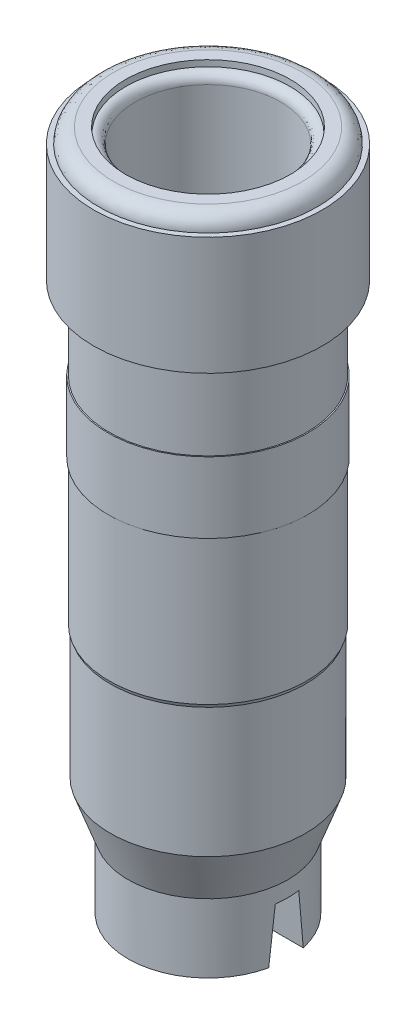
SolidWorks part; units mm, degrees
ref_plane "Front" through (0, 0, 0) normal (0, 0, 1) x (1, 0, 0)
ref_plane "Top" through (0, 0, 0) normal (0, 1, 0) x (1, 0, 0)
ref_plane "Right" through (0, 0, 0) normal (1, 0, 0) x (0, 0, -1)
sketch "Esboço1" plane through (0, 0, 0) normal (0, 0, 1) x (1, 0, 0)
  line L0 (0, 0) -> (0, 23.1) construction
  line L6 (-3.37, 10.5013) -> (-3.41, 10.5013)
  line L7 (-3.9, 18.6) -> (-3.37, 18.6)
  line L8 (-3.37, 18.6) -> (-3.37, 15.8)
  line L9 (-3.37, 4.1013) -> (-2.725, 2.3292)
  line L10 (-2.725, 2.3292) -> (-2.725, 0)
  line L15 (-3.37, 15.8) -> (-3.43, 15.8)
  line L16 (-3.37, 13.4) -> (-3.43, 13.4)
  line L17 (-3.41, 10.5013) -> (-3.41, 8.1013)
  line L18 (-3.41, 8.1013) -> (-3.37, 8.1013)
  line L19 (-3.37, 13.4) -> (-3.37, 10.5013)
  line L20 (-3.37, 8.1013) -> (-3.37, 4.1013)
  line L21 (-3.43, 13.4) -> (-3.43, 15.8)
  line L22 (-3.9, 22.6) -> (-3.9, 18.6)
  line L23 (-2.725, 0) -> (0, 0)
  line L24 (-3.9, 22.6) -> (-3.725, 22.6)
  line L25 (0, 23.1) -> (0, 0) construction
  line L27 (-3.225, 23.1) -> (0, 23.1)
  line L29 (0, 23.1) -> (0, 0)
  arc A1 (-3.225, 23.1) -> (-3.725, 22.6) centre (-3.225, 22.6) ccw
  point P5 (-3.725, 23.1)
  point P20 (-3.37, 17.2)
  dimension "D9" = 0.5
  dimension "D8" = 1
  dimension "D3" = 22.6
  dimension "D4" = 4
  dimension "D5" = 5.45
  dimension "D6" = 20.2708
  dimension "D7" = 0.5
  dimension "D10" = 0.5
  dimension "D11" = 2.8
  dimension "D12" = 2.4
  dimension "D13" = 20
  dimension "D14" = 3.725
  dimension "D16" = 7.8
  dimension "D17" = 0.06
  dimension "D18" = 6.74
  dimension "D19" = 2.4
  dimension "D20" = 4
  dimension "D21" = 6.74
  dimension "D22" = 0.04
  dimension "D23" = 6.82
  dimension "D24" = 6.86
revolve "Revolução1" add sketch "Esboço1" angle 360 about L0
sketch "Esboço3" plane through (0, 0, 0) normal (0, -1, 0) x (1, 0, 0)
  circle A0 centre (0, 0) radius 1.5
  dimension "D1" = 3
extrude "Corte-extrusão1" cut sketch "Esboço3" against normal blind 1.8
sketch "Esboço5" plane through (0, 0, 0) normal (1, 0, 0) x (0, 0, -1)
  line L0 (0, 0) -> (0, 22.6) construction
  line L1 (-1.5, 0) -> (1.5, 0) construction
  line L2 (3.9, 22.6) -> (-3.9, 22.6) construction
  line L3 (-0.5892, 0) -> (0.5892, 0)
  line L4 (0.5892, 0) -> (0.4, 1.8)
  line L5 (0.4, 1.8) -> (-0.4, 1.8)
  line L6 (-0.5892, 0) -> (-0.4, 1.8)
  point P10 (0, 1.8)
  dimension "D1" = 0.8
  dimension "D2" = 1.8
  dimension "D3" = 6
extrude "Corte-extrusão2" cut sketch "Esboço5" against normal through all both and the other way through all
sketch "Esboço6" plane through (0, 0, 0) normal (0, 0, 1) x (1, 0, 0)
  line L0 (3.9, 22.6) -> (-3.9, 22.6) construction
  line L1 (2.8105, 23.1) -> (0, 23.1)
  line L2 (0, 22.6) -> (0, 0) construction
  line L3 (0, 23.1) -> (0, 22.6)
  line L4 (2.46, 10.9) -> (2.26, 10.9)
  line L5 (2.48, 22.6) -> (2.48, 17.9)
  line L6 (2.45, 9.1035) -> (1.75, 6.4911)
  line L7 (1.75, 6.4911) -> (1.75, 3.4)
  line L8 (1.75, 3.4) -> (1.5, 3.4)
  line L9 (2.8, 22.8993) -> (2.8105, 23.1)
  line L10 (0, 22.6) -> (0, 23.1) construction
  line L11 (3.225, 23.1) -> (-3.225, 23.1) construction
  line L12 (0, 22.6) -> (0, 3.9)
  line L14 (2.26, 10.9) -> (2.45, 9.8225)
  line L15 (2.465, 13.2) -> (2.265, 13.2)
  line L16 (2.265, 13.2) -> (2.46, 12.0941)
  line L17 (2.48, 17.9) -> (2.28, 17.9)
  line L18 (2.28, 17.9) -> (2.48, 16.7657)
  line L19 (2.45, 9.8225) -> (2.45, 9.1035)
  line L20 (2.46, 12.0941) -> (2.46, 10.9)
  line L21 (2.48, 16.7657) -> (2.465, 13.2)
  line L22 (-2.6605, 0) -> (2.6605, 0) construction
  line L23 (0, 0) -> (0, 3.4) construction
  arc A0 (2.48, 22.6) -> (2.8, 22.8993) centre (2.78, 22.6) cw
  arc A1 (1.5, 3.4) -> (0, 3.9) centre (0, 1.4) ccw
  dimension "D7" = 0.2
  dimension "D16" = 15
  dimension "D10" = 0.2
  dimension "D19" = 0.3
  dimension "D14" = 2.5
  dimension "D3" = 9.4
  dimension "D4" = 10
  dimension "D5" = 0.2
  dimension "D6" = 11.7
  dimension "D8" = 10
  dimension "D9" = 15
  dimension "D11" = 10
  dimension "D12" = 3.0911
  dimension "D13" = 0.5
  dimension "D15" = 19.7
  dimension "D17" = 3.5
  dimension "D18" = 3
  dimension "D20" = 5.6
  dimension "D21" = 3
  dimension "D22" = 4.7
  dimension "D23" = 2.48
  dimension "D24" = 2.46
  dimension "D25" = 2.46
  dimension "D26" = 4.93
  dimension "D27" = 4.9
  dimension "D28" = 4.9
revolve "Corte-Revolução1" cut sketch "Esboço6" angle 360 about L2
fillet "Filete1" radius 0.2 1 edges at (-1.75, 3.4, 0)
sketch "Esboço9" plane through (0, 0, 0) normal (0, 0, 1) x (1, 0, 0)
  line L0 (0, 0) -> (0, 43.223) construction
  line L5 (-6.0049, 22.6) -> (-3.9, 22.6)
  line L6 (-3.37, 8.4914) -> (-3.33, 8.3815)
  line L7 (-3.9, 18.6) -> (-3.37, 18.6)
  line L8 (-3.37, 18.6) -> (-3.37, 15.8)
  line L9 (-3.33, 3.9914) -> (-2.725, 2.3292)
  line L15 (-3.37, 15.8) -> (-3.41, 15.8)
  line L16 (-3.37, 13.4) -> (-3.41, 13.4)
  line L17 (-3.33, 8.3815) -> (-3.33, 3.9914)
  line L18 (-2.6605, 0) -> (2.6605, 0) construction
  line L19 (-2.725, 2.3292) -> (-2.725, 1.8) construction
  line L20 (-3.37, 13.4) -> (-3.37, 8.4914)
  line L21 (-3.41, 13.4) -> (-3.41, 15.8)
  line L22 (-3.37, 4.1013) -> (-2.725, 2.3292) construction
  line L23 (-3.9, 22.6) -> (-3.9, 18.6)
  line L26 (-3.9, 18.6) -> (3.9, 18.6) construction
  line L27 (-6.0049, 22.6) -> (-6.0049, 2.3292)
  line L28 (-6.0049, 2.3292) -> (-2.725, 2.3292)
  point P21 (-3.37, 17.2)
  dimension "D3" = 6.74
  dimension "D4" = 6.66
  dimension "D5" = 4.5
  dimension "D8" = 4
  dimension "D9" = 7.8
  dimension "D17" = 20
  dimension "D18" = 20
  dimension "D19" = 2.4
  dimension "2,65" = 2.8
  dimension "0,05" = 0.04
revolve "Corte-Revolução2" cut sketch "Esboço9" angle 360 about L0
scale "Escala1" scale about centroid uniform scaling no x scale factor 0.98 y scale factor 0.985 z scale factor 0.98
